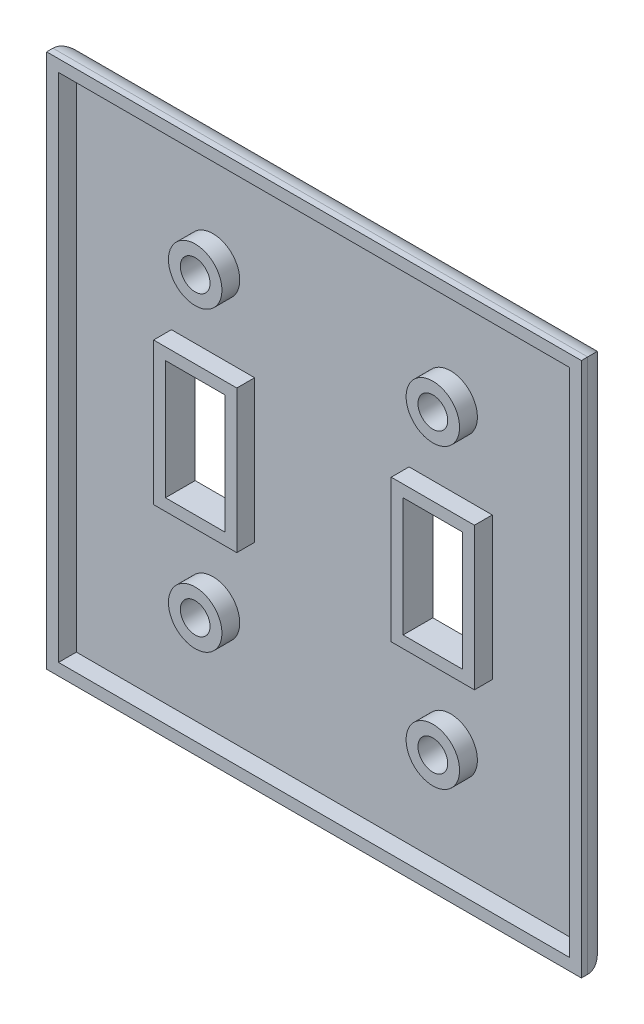
SolidWorks part; units mm, degrees
ref_plane "Front" through (0, 0, 0) normal (0, 0, 1) x (1, 0, 0)
ref_plane "Top" through (0, 0, 0) normal (0, 1, 0) x (1, 0, 0)
ref_plane "Right" through (0, 0, 0) normal (1, 0, 0) x (0, 0, -1)
sketch "Sketch2" plane through (0, 0, 0) normal (0, 0, 1) x (1, 0, 0)
  line L1 (0, 0) -> (114.3, 0)
  line L2 (0, 0) -> (0, 114.3)
  line L3 (0, 114.3) -> (114.3, 114.3)
  line L4 (114.3, 0) -> (114.3, 114.3)
  dimension "D1" = 114.3
  dimension "D2" = 114.3
extrude "Boss-Extrude1" add sketch "Sketch2" along normal blind 6.35
sketch "Sketch3" plane through (0, 0, 6.35) normal (0, 0, 1) x (1, 0, 0)
  line L0 (76.2, 69.85) -> (88.9, 69.85)
  line L1 (25.4, 69.85) -> (38.1, 69.85)
  line L2 (25.4, 69.85) -> (25.4, 44.45)
  line L3 (25.4, 44.45) -> (38.1, 44.45)
  line L4 (38.1, 69.85) -> (38.1, 44.45)
  line L5 (76.2, 69.85) -> (76.2, 44.45)
  line L6 (76.2, 44.45) -> (88.9, 44.45)
  line L7 (88.9, 69.85) -> (88.9, 44.45)
  line L8 (114.3, 114.3) -> (0, 114.3) construction
  line L9 (0, 114.3) -> (0, 0) construction
  line L11 (114.3, 0) -> (114.3, 114.3) construction
  circle A0 centre (31.75, 25.4) radius 3.175
  circle A1 centre (82.55, 88.9) radius 3.175
  circle A2 centre (82.55, 25.4) radius 3.175
  circle A4 centre (31.75, 88.9) radius 3.175
  dimension "D1" = 6.35
  dimension "D2" = 12.7
  dimension "D6" = 25.4
  dimension "D3" = 25.4
  dimension "D4" = 25.4
  dimension "D5" = 31.75
  dimension "D7" = 31.75
  dimension "D8" = 31.75
  dimension "D9" = 25.4
  dimension "D10" = 25.4
  dimension "D11" = 19.05
  dimension "D12" = 19.05
  dimension "D13" = 25.4
extrude "Cut-Extrude1" cut sketch "Sketch3" against normal through all contours A4
extrude "Cut-Extrude2" cut sketch "Sketch3<3>" against normal through all contours A1
sketch "Sketch3<3>" plane through (0, 0, 6.35) normal (0, 0, 1) x (1, 0, 0) same geometry as "Sketch3"
extrude "Cut-Extrude3" cut sketch "Sketch3<4>" against normal through all contours A0
sketch "Sketch3<4>" plane through (0, 0, 6.35) normal (0, 0, 1) x (1, 0, 0) same geometry as "Sketch3"
extrude "Cut-Extrude4" cut sketch "Sketch3<5>" against normal through all contours L4 L3 L2 L1
sketch "Sketch3<5>" plane through (0, 0, 6.35) normal (0, 0, 1) x (1, 0, 0) same geometry as "Sketch3"
extrude "Cut-Extrude5" cut sketch "Sketch3<6>" against normal through all contours L5 L6 L7 L0
sketch "Sketch3<6>" plane through (0, 0, 6.35) normal (0, 0, 1) x (1, 0, 0) same geometry as "Sketch3"
extrude "Cut-Extrude6" cut sketch "Sketch3<7>" against normal through all contours A2
sketch "Sketch3<7>" plane through (0, 0, 6.35) normal (0, 0, 1) x (1, 0, 0) same geometry as "Sketch3"
ref_plane "Plane1" through (114.3, 0, 6.35) normal (0, 0, -1) x (-1, 0, 0)
shell "Shell1" thickness 2.54 removed face at (85.725, 25.4, 6.35)
fillet "Fillet1" radius 5 4 edges at (0, 57.15, 0) (57.15, 0, 0) (114.3, 57.15, 0) (57.15, 114.3, 0)
